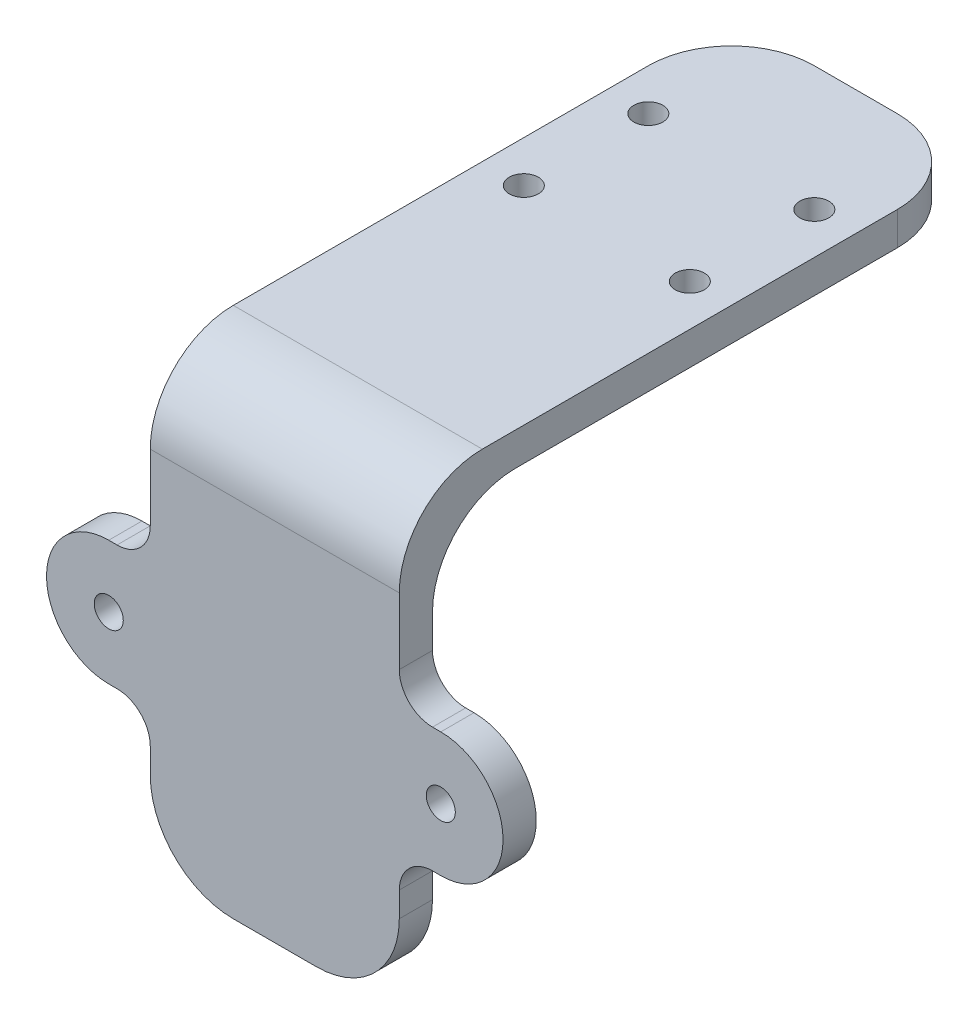
SolidWorks part; units mm, degrees
ref_plane "Piano frontale" through (0, 0, 0) normal (0, 0, 1) x (1, 0, 0)
ref_plane "Piano superiore" through (0, 0, 0) normal (0, 1, 0) x (1, 0, 0)
ref_plane "Piano destro" through (0, 0, 0) normal (1, 0, 0) x (0, 0, -1)
sketch "Sketch1" plane through (0, 0, 0) normal (0, 1, 0) x (1, 0, 0)
  line L1 (-15, -35) -> (15, -35)
  line L2 (-15, -35) -> (-15, 35)
  line L3 (-15, 35) -> (15, 35)
  line L4 (15, -35) -> (15, 35)
  line L5 (-15, -35) -> (15, 35) construction
  line L6 (-15, 35) -> (15, -35) construction
  point P0 (0, 0)
  dimension "D1" = 70
  dimension "D2" = 30
extrude "Boss-Extrude1" add sketch "Sketch1" along normal mid plane 4
sketch "Sketch2" plane through (0, -2, 0) normal (0, -1, 0) x (1, 0, 0)
  line L0 (-15, -35) -> (-15, 35) construction
  line L1 (15, 35) -> (-15, 35)
  line L2 (15, 35) -> (15, 31)
  line L3 (15, 31) -> (-15, 31)
  line L4 (-15, 35) -> (-15, 31)
  dimension "D1" = 4
extrude "Boss-Extrude2" add sketch "Sketch2" along normal blind 50
ref_axis "Axis1" through (0, 4.7, 35) along (0, -1, 0)
sketch "Sketch3" plane through (0, 0, 35) normal (0, 0, 1) x (1, 0, 0)
  line L1 (20, -20) -> (-20, -20)
  line L3 (20, -35) -> (-20, -35)
  line L5 (-20, -27.5) -> (20, -27.5) construction
  line L6 (-15, 2) -> (15, 2) construction
  line L7 (0, -29.7) -> (0, 29.7) construction
  line L8 (0, 4.7) -> (0, -54.7) construction
  circle A0 centre (-20, -27.5) radius 1.75
  arc A1 (-20, -35) -> (-20, -20) centre (-20, -27.5) cw
  arc A2 (20, -35) -> (20, -20) centre (20, -27.5) ccw
  circle A3 centre (20, -27.5) radius 1.75
  point P0 (0, -28)
  dimension "D2" = 3.5
  dimension "D1" = 29.5
  dimension "D3" = 20
extrude "Boss-Extrude3" add sketch "Sketch3" against normal up to surface (4 mm away) up to face at (0, -27, 31)
sketch "Sketch4" plane through (0, 2, 0) normal (0, 1, 0) x (1, 0, 0)
  line L0 (-29.7, 0) -> (29.7, 0) construction
  line L1 (0, -29.7) -> (0, 29.7) construction
  circle A0 centre (-10, 20) radius 1.75
  dimension "D1" = 20
  dimension "D2" = 10
extrude "Cut-Extrude1" cut sketch "Sketch4" against normal up to surface (4 mm away) up to face at (0, -2, -2)
pattern_linear "LPattern1" count 2 spacing 15 along (0, 0, 1) count 2 spacing 20 along (1, 0, 0) of "Cut-Extrude1"
fillet "Fillet1" radius 10 6 edges at (0, -2, 31) (0, 2, 35) (15, 0, -35) (-15, 0, -35) (-15, -52, 33) (15, -52, 33)
fillet "Fillet2" radius 4 4 edges at (15, -35, 33) (15, -20, 33) (-15, -20, 33) (-15, -35, 33)
